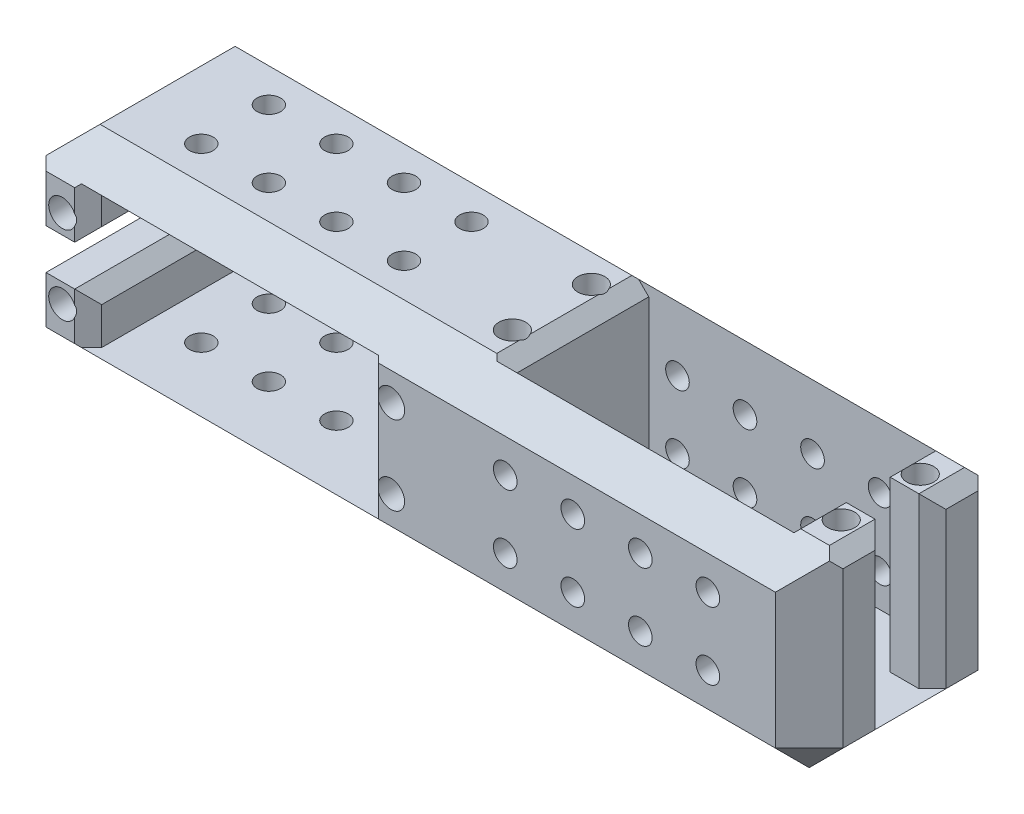
SolidWorks part; units mm, degrees
ref_plane "前视基准面" through (0, 0, 0) normal (0, 0, 1) x (1, 0, 0)
ref_plane "上视基准面" through (0, 0, 0) normal (0, 1, 0) x (1, 0, 0)
ref_plane "右视基准面" through (0, 0, 0) normal (1, 0, 0) x (0, 0, -1)
other "Configuration Table"
sketch "Sketch1" plane through (0, 0, 0) normal (0, 0, 1) x (1, 0, 0)
  line L1 (-28.75, -15) -> (28.75, -15)
  line L2 (-28.75, -15) -> (-28.75, 15)
  line L3 (-28.75, 15) -> (28.75, 15)
  line L4 (28.75, -15) -> (28.75, 15)
  line L5 (-28.75, -15) -> (28.75, 15) construction
  line L6 (-28.75, 15) -> (28.75, -15) construction
  point P0 (0, 0)
  dimension "D1" = 57.5
  dimension "D2" = 30
extrude "Boss-Extrude1" add sketch "Sketch1" along normal blind 30
sketch "Sketch2" plane through (0, 0, 30) normal (0, 0, 1) x (1, 0, 0)
  line L1 (-20.5, -10.5) -> (20.5, -10.5)
  line L2 (-20.5, -10.5) -> (-20.5, 10.5)
  line L3 (-20.5, 10.5) -> (20.5, 10.5)
  line L4 (20.5, -10.5) -> (20.5, 10.5)
  line L5 (-20.5, -10.5) -> (20.5, 10.5) construction
  line L6 (-20.5, 10.5) -> (20.5, -10.5) construction
  point P0 (0, 0)
  dimension "D1" = 41
  dimension "D2" = 21
extrude "Cut-Extrude1" cut sketch "Sketch2" against normal blind 25
ref_plane "Plane1" through (0, 0, 15) normal (0, 0, 1) x (1, 0, 0)
sketch "Sketch8" plane through (0, 0, 30) normal (0, 0, 1) x (1, 0, 0)
  line L0 (0, 0) -> (24.35, 0) construction
  line L1 (24.35, 0) -> (24.35, 5.85) construction
  line L2 (0, 0) -> (0, 15) construction
  line L3 (28.75, 15) -> (-28.75, 15) construction
  circle A0 centre (24.35, 5.85) radius 2
  circle A1 centre (24.35, -5.85) radius 2
  circle A2 centre (-24.35, -5.85) radius 2
  circle A3 centre (-24.35, 5.85) radius 2
  dimension "D3" = 4
  dimension "D1" = 5.85
  dimension "D2" = 24.35
extrude "Cut-Extrude6" cut sketch "Sketch8" against normal blind 10
sketch "Sketch9" plane through (0, 0, 30) normal (0, 0, 1) x (1, 0, 0)
  line L0 (-20.5, 0) -> (-28.75, 0) construction
  line L1 (-20.5, 10.5) -> (-20.5, -10.5) construction
  line L2 (-28.75, 15) -> (-28.75, -15) construction
  line L3 (-28.75, 0) -> (-24.625, 0) construction
  line L5 (-28.75, -3) -> (-20.5, -3)
  line L6 (-28.75, -3) -> (-28.75, 3)
  line L7 (-28.75, 3) -> (-20.5, 3)
  line L8 (-20.5, -3) -> (-20.5, 3)
  line L9 (-28.75, -3) -> (-20.5, 3) construction
  line L10 (-28.75, 3) -> (-20.5, -3) construction
  dimension "D1" = 6
extrude "Cut-Extrude7" cut sketch "Sketch9" against normal blind 25
sketch "Sketch10" plane through (0, 0, 5) normal (0, 0, 1) x (1, 0, 0)
  line L0 (0, 0) -> (-10, 0) construction
  circle A0 centre (-10, 0) radius 5
  dimension "D2" = 10
  dimension "D1" = 10
extrude "Cut-Extrude8" cut sketch "Sketch10" against normal blind 10
sketch "Sketch11" plane through (28.75, 0, 0) normal (1, 0, 0) x (0, 0, -1)
  line L0 (-30, 0) -> (0, 0) construction
  line L1 (-30, -15) -> (-30, 15) construction
  line L2 (0, 0) -> (-15, 0) construction
  line L4 (-30, -15) -> (0, -15)
  line L5 (-30, -15) -> (-30, 15)
  line L6 (-30, 15) -> (0, 15)
  line L7 (0, -15) -> (0, 15)
  line L8 (-30, -15) -> (0, 15) construction
  line L9 (-30, 15) -> (0, -15) construction
  dimension "D1" = 30
  dimension "D2" = 30
extrude "Boss-Extrude2" add sketch "Sketch11" along normal blind 57.5
sketch "Sketch14" plane through (0, 15, 0) normal (0, 1, 0) x (1, 0, 0)
  line L0 (28.75, 0) -> (28.75, -30) construction
  line L1 (86.25, 0) -> (-28.75, 0) construction
  line L2 (86.25, -30) -> (-28.75, -30) construction
  line L4 (28.75, -15) -> (86.25, -15) construction
  line L7 (86.25, 0) -> (86.25, -30) construction
  line L8 (86.25, -15) -> (57.5, -15) construction
  line L9 (57.5, -15) -> (81.85, -15) construction
  line L14 (81.85, -15) -> (81.85, -9.15) construction
  line L15 (57.5, -15) -> (57.5, -24.9554) construction
  circle A4 centre (81.85, -9.15) radius 2
  circle A5 centre (81.85, -20.85) radius 2
  circle A6 centre (33.15, -20.85) radius 2
  circle A7 centre (33.15, -9.15) radius 2
  dimension "D3" = 24.35
  dimension "D1" = 4
  dimension "D2" = 5.85
extrude "Cut-Extrude14" cut sketch "Sketch14" against normal blind 15
sketch "Sketch18" plane through (0, 15, 0) normal (0, 1, 0) x (1, 0, 0)
  line L0 (28.75, 0) -> (28.75, -30) construction
  line L1 (86.25, 0) -> (-28.75, 0) construction
  line L2 (86.25, -30) -> (-28.75, -30) construction
  line L3 (28.75, -30) -> (28.75, -15) construction
  line L4 (28.75, -15) -> (86.25, -15) construction
  line L5 (86.25, 0) -> (86.25, -30) construction
  line L6 (86.25, -15) -> (57.5, -15) construction
  line L7 (78, -15) -> (86.25, -15) construction
  line L8 (37, -25.5) -> (78, -25.5)
  line L9 (37, -25.5) -> (37, -4.5)
  line L10 (37, -4.5) -> (78, -4.5)
  line L11 (78, -25.5) -> (78, -4.5)
  line L12 (37, -25.5) -> (78, -4.5) construction
  line L13 (37, -4.5) -> (78, -25.5) construction
  line L14 (86.25, -15) -> (82.125, -15) construction
  line L16 (78, -18.25) -> (86.25, -18.25)
  line L17 (78, -18.25) -> (78, -11.75)
  line L18 (78, -11.75) -> (86.25, -11.75)
  line L19 (86.25, -18.25) -> (86.25, -11.75)
  line L20 (78, -18.25) -> (86.25, -11.75) construction
  line L21 (78, -11.75) -> (86.25, -18.25) construction
  line M14 (86.25, -30) -> (86.25, 0)
  dimension "D1" = 41
  dimension "D2" = 21
  dimension "D3" = 6.5
extrude "Cut-Extrude15" cut sketch "Sketch18" against normal blind 25 contours L8 L11 L10 L9 | L18 L11 L16 M14 region at (57.5, 15, 15) region at (82.125, 15, 15)
sketch "Sketch19" plane through (0, -15, 0) normal (0, -1, 0) x (1, 0, 0)
  line L0 (28.75, 30) -> (28.75, 0) construction
  line L1 (-28.75, 30) -> (86.25, 30) construction
  line L2 (-28.75, 0) -> (86.25, 0) construction
  line L3 (28.75, 0) -> (28.75, 15) construction
  line L4 (28.75, 15) -> (86.25, 15) construction
  line L5 (16.5, 15) -> (-16.5, 15) construction
  line L6 (86.25, 15) -> (57.5, 15) construction
  line L7 (57.5, 15) -> (67.5, 15) construction
  circle A0 centre (67.5, 15) radius 5
  dimension "D2" = 10
  dimension "D1" = 10
  dimension "D3" = 28.75
extrude "Cut-Extrude16" cut sketch "Sketch19" against normal blind 25
chamfer "Chamfer4" distance 5 angle 45 10 edges at (28.75, -15, 0) (28.75, -15, 30) (28.75, 15, 30) (86.25, 0, 30) (86.25, -15, 15) (86.25, 0, 0) (28.75, 15, 0) (-28.75, 15, 15) (-28.75, 0, 0) (-28.75, -15, 15)
chamfer "Chamfer5" distance 2 angle 45 18 edges at (78, 15, 8.375) (78, 2.5, 11.75) (86.25, 15, 8.375) (86.25, 2.5, 11.75) (78, 15, 21.625) (78, 2.5, 18.25) (86.25, 15, 21.625) (86.25, 2.5, 18.25) (-28.75, -6.5, 30) (-28.75, -3, 17.5) (-20.5, -6.5, 30) (-20.5, -3, 17.5) (-28.75, 6.5, 30) (-28.75, 3, 17.5) (-20.5, 6.5, 30) (-20.5, 3, 17.5) (20.5, 0, 30) (37, 15, 15)
sketch "Sketch23" plane through (0, 0, 30) normal (0, 0, 1) x (1, 0, 0)
  line L0 (81.25, 0) -> (71.25, 0) construction
  line L1 (81.25, -10) -> (81.25, 10) construction
  line L2 (71.25, 0) -> (71.25, 5) construction
  circle A0 centre (71.25, 5) radius 1.75
  circle A1 centre (71.25, -5) radius 1.75
  circle A2 centre (61.25, 5) radius 1.75
  circle A3 centre (61.25, -5) radius 1.75
  circle A4 centre (51.25, 5) radius 1.75
  circle A5 centre (51.25, -5) radius 1.75
  circle A6 centre (41.25, 5) radius 1.75
  circle A7 centre (41.25, -5) radius 1.75
  circle A10 centre (31.25, 5) radius 1.75 [skipped]
  circle A11 centre (31.25, -5) radius 1.75 [skipped]
  dimension "D1" = 3.5
  dimension "D2" = 5
  dimension "D3" = 10
  dimension "D5" = 10
  dimension "D4" = 5
extrude "Cut-Extrude19" cut sketch "Sketch23" against normal through all
sketch "Sketch24" plane through (0, 15, 0) normal (0, 1, 0) x (1, 0, 0)
  line L2 (-23.75, -15) -> (-13.75, -15) construction
  line L3 (-23.75, -5) -> (-23.75, -25) construction
  line L4 (-16.5, -15) -> (16.5, -15) construction
  line L5 (-13.75, -15) -> (-13.75, -10) construction
  line L6 (-3.75, -15) -> (-3.75, -10) construction
  line L7 (6.25, -15) -> (6.25, -10) construction
  line L8 (16.25, -15) -> (16.25, -10) construction
  circle A8 centre (-13.75, -10) radius 1.75
  circle A9 centre (-13.75, -20) radius 1.75
  circle A10 centre (-3.75, -10) radius 1.75
  circle A11 centre (-3.75, -20) radius 1.75
  circle A12 centre (6.25, -10) radius 1.75
  circle A13 centre (6.25, -20) radius 1.75
  circle A14 centre (16.25, -10) radius 1.75
  circle A15 centre (16.25, -20) radius 1.75
  dimension "D1" = 10
  dimension "D5" = 3.5
  dimension "D6" = 5
  dimension "D7" = 10
  dimension "D8" = 4
extrude "Cut-Extrude20" cut sketch "Sketch24" against normal through all
sketch "Sketch26" plane through (0, 0, 5) normal (0, 0, 1) x (1, 0, 0)
  circle A0 centre (-10, 0) radius 7.5
  dimension "D1" = 15
extrude "Cut-Extrude21" cut sketch "Sketch26" against normal blind 2.5
sketch "Sketch27" plane through (0, -10, 0) normal (0, 1, 0) x (1, 0, 0)
  circle A0 centre (67.5, -15) radius 7.5
  dimension "D1" = 15
extrude "Cut-Extrude22" cut sketch "Sketch27" against normal blind 2.5
